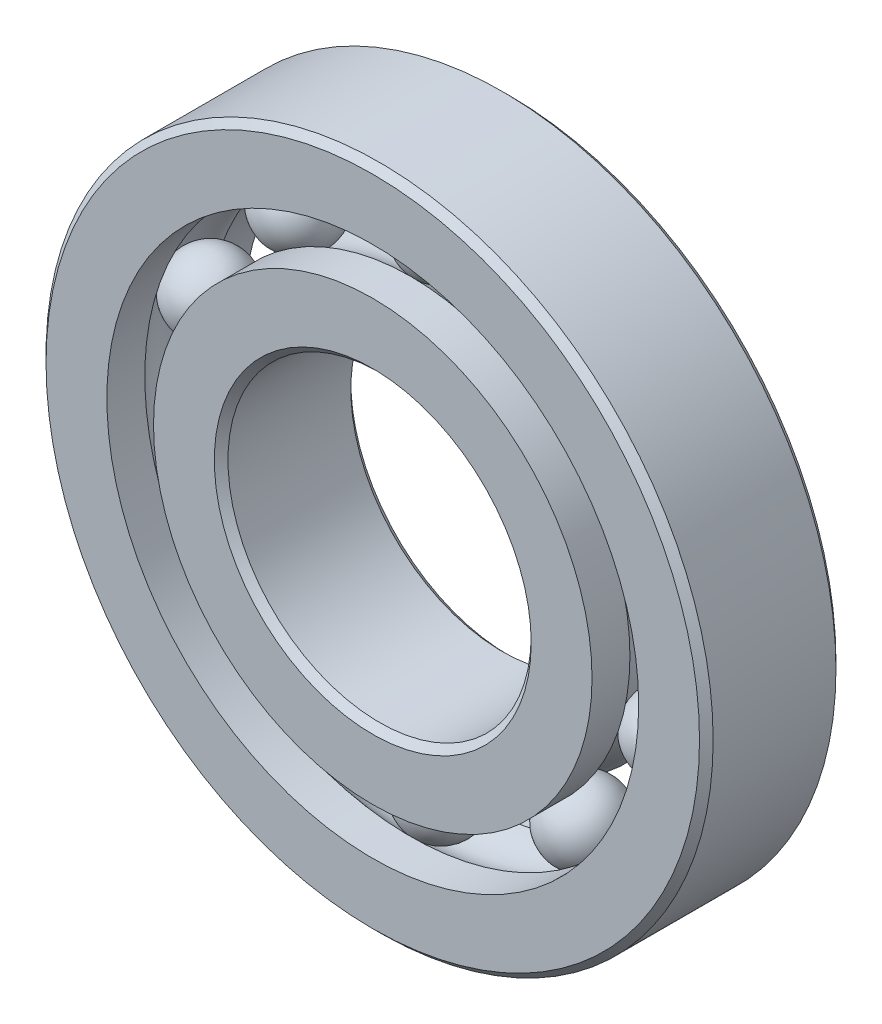
SolidWorks part; units mm, degrees
ref_plane "Front Plane" through (0, 0, 0) normal (0, 0, 1) x (1, 0, 0)
ref_plane "Top Plane" through (0, 0, 0) normal (0, 1, 0) x (1, 0, 0)
ref_plane "Right Plane" through (0, 0, 0) normal (1, 0, 0) x (0, 0, -1)
sketch "Sketch1" plane through (0, 0, 0) normal (1, 0, 0) x (0, 0, -1)
  line L0 (-3.5719, 0) -> (3.5719, 0) construction
  line L1 (0, 17.4625) -> (0, -17.4625) construction
  line L2 (3.2147, 17.4625) -> (-3.2147, 17.4625)
  line L3 (-3.2147, 17.4625) -> (-3.5719, 17.1053)
  line L4 (-3.5719, 17.1053) -> (-3.5719, 13.9212)
  line L5 (-3.5719, 13.9212) -> (-1.5875, 13.9212)
  line L6 (3.5719, 13.9212) -> (1.5875, 13.9212)
  line L7 (3.5719, 17.1053) -> (3.5719, 13.9212)
  line L8 (3.2147, 17.4625) -> (3.5719, 17.1053)
  line L9 (0, 17.4625) -> (0, 12.7) construction
  line L10 (0, 12.7) -> (0, 7.9375) construction
  arc A0 (-1.5875, 13.9212) -> (1.5875, 13.9212) centre (0, 12.7) cw
  point P14 (0, 7.9375)
  dimension "D3" = 3.175
  dimension "D1" = 45
  dimension "Width" = 7.1437
  dimension "OD" = 34.925
  dimension "D2" = 0.3572
  dimension "Shaft Dia" = 15.875
  dimension "D4" = 1.2212
revolve "Revolve1" add sketch "Sketch1" angle 360 about L0
sketch "Sketch3" plane through (0, 0, 0) normal (1, 0, 0) x (0, 0, -1)
  line L0 (-3.5719, 11.4788) -> (-1.5875, 11.4788)
  line L1 (0, 17.4625) -> (0, -17.4625) construction
  line L2 (-3.5719, 17.1053) -> (-3.5719, 13.9212) construction
  line L3 (-3.5719, 11.4788) -> (-3.5719, 8.2947)
  line L4 (-3.2147, 17.4625) -> (-3.5719, 17.1053) construction
  line L5 (-3.5719, 8.2947) -> (-3.2147, 7.9375)
  line L6 (-3.2147, 7.9375) -> (3.2147, 7.9375)
  line L7 (3.2147, 17.4625) -> (3.2147, -17.4625) construction
  line L8 (3.2147, 7.9375) -> (3.5719, 8.2947)
  line L9 (3.5719, -17.1053) -> (3.5719, 17.1053) construction
  line L10 (3.5719, 8.2947) -> (3.5719, 11.4788)
  line L11 (3.5719, 11.4788) -> (1.5875, 11.4788)
  line L13 (3.2147, 17.4625) -> (3.5719, 17.1053) construction
  arc A0 (1.5875, 13.9212) -> (-1.5875, 13.9212) centre (0, 12.7) ccw construction
  arc A1 (1.5875, 11.4788) -> (-1.5875, 11.4788) centre (0, 12.7) cw
revolve "Revolve3" add sketch "Sketch3" angle 360 about L0
sketch "Sketch4" plane through (0, 0, 0) normal (1, 0, 0) x (0, 0, -1)
  line L0 (-2.0028, 12.7) -> (2.0028, 12.7)
  arc A2 (-2.0028, 12.7) -> (2.0028, 12.7) centre (0, 12.7) cw
  arc A3 (1.5875, 13.9212) -> (-1.5875, 13.9212) centre (0, 12.7) ccw construction
revolve "Revolve4" add sketch "Sketch4" angle 360 about L0
ref_axis "Axis1" through (0, 0, -3.5719) along (0, 0, 1)
pattern_circular "CirPattern1" count 10 over 360 about axis through (0, 0, -3.5719) along (0, 0, 1) of bodies 104
sketch "Sketch5" plane through (0, 0, 0) normal (1, 0, 0) x (0, 0, -1)
  line L0 (-3.5719, 13.9212) -> (-1.5875, 13.9212) construction
  line L1 (-3.3933, 13.9212) -> (-2.0028, 13.9212)
  line L2 (-3.3933, 13.9212) -> (-3.3933, 11.4788)
  line L3 (-3.3933, 11.4788) -> (-2.0028, 11.4788)
  line L4 (-2.0028, 13.9212) -> (-2.0028, 11.4788)
  line L5 (-3.5719, 11.4788) -> (-1.5875, 11.4788) construction
  line L6 (3.5719, 13.9212) -> (1.5875, 13.9212) construction
  line L7 (3.3933, 13.9212) -> (2.0028, 13.9212)
  line L8 (3.3933, 13.9212) -> (3.3933, 11.4788)
  line L9 (3.3933, 11.4788) -> (2.0028, 11.4788)
  line L10 (2.0028, 13.9212) -> (2.0028, 11.4788)
  line L11 (3.5719, 11.4788) -> (1.5875, 11.4788) construction
  line L12 (-3.2147, 17.4625) -> (-3.5719, 17.1053) construction
  point P18 (-3.3933, 17.2839)
revolve "Revolve5" [suppressed] add sketch "Sketch5" angle 360 about L0
equation "\"D2@Sketch1\" = \"Width@Sketch1\"*.05"
equation "\"D3@Sketch1\" = \"Width@Sketch1\"/2.25"
equation "\"D4@Sketch1\" = (((\"OD@Sketch1\"-\"Width@Sketch1\")/2)/3.25)/3.5"
equation "\"D2@CirPattern1\" = 360/\"Balls@CirPattern1\""
